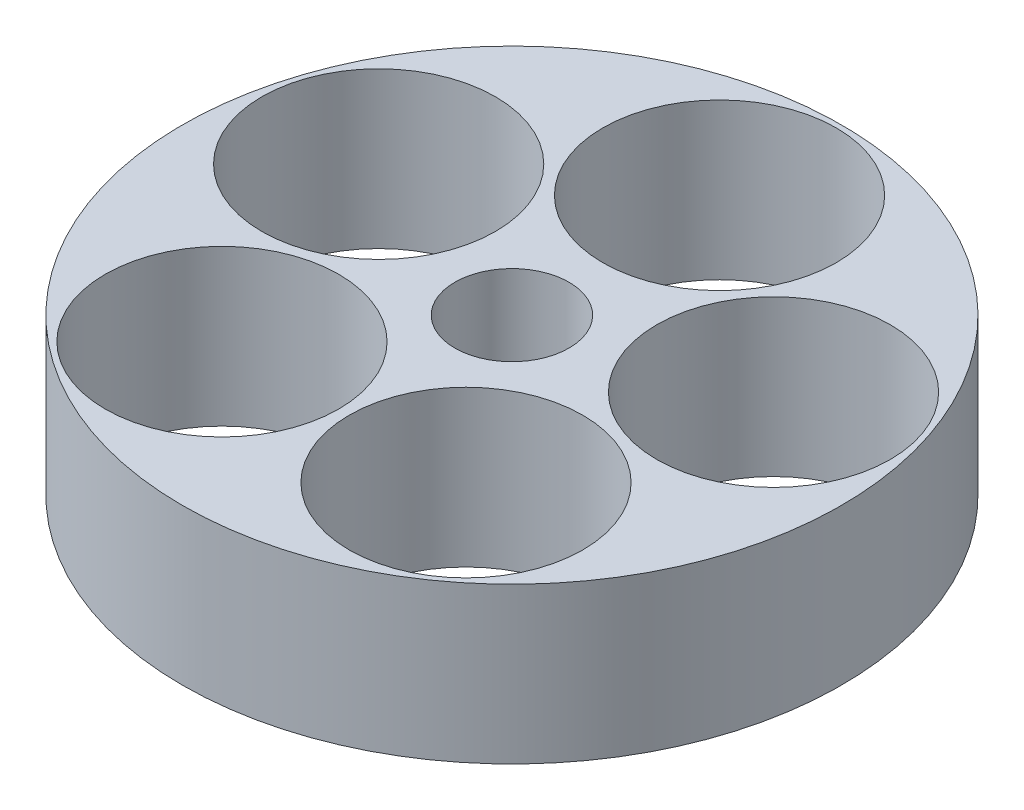
SolidWorks part; units mm, degrees
ref_plane "Front Plane" through (0, 0, 0) normal (0, 0, 1) x (1, 0, 0)
ref_plane "Top Plane" through (0, 0, 0) normal (0, 1, 0) x (1, 0, 0)
ref_plane "Right Plane" through (0, 0, 0) normal (1, 0, 0) x (0, 0, -1)
sketch "Sketch1" plane through (0, 0, 0) normal (0, 1, 0) x (1, 0, 0)
  line L0 (0, -164.5173) -> (0, 163.7587) construction
  line L1 (-104.9541, 34.1017) -> (106.3821, -34.5656) construction
  line L2 (-169.6132, -123.2312) -> (93.1873, 67.7046) construction
  line L3 (-107.5036, 0) -> (118.5963, 0) construction
  line L4 (-102.8693, -33.4243) -> (102.8693, 33.4243) construction
  line L5 (-62.7697, -86.3951) -> (62.7697, 86.3951) construction
  circle A0 centre (0, 0) radius 63.5
  circle A1 centre (38.0423, 12.3607) radius 22.5
  circle A4 centre (0, 40) radius 22.5
  circle A5 centre (-38.0423, 12.3607) radius 22.5
  circle A6 centre (-23.5114, -32.3607) radius 22.5
  circle A10 centre (23.5114, -32.3607) radius 22.5
  circle A11 centre (0, 0) radius 11
  dimension "D1" = 127
  dimension "D4" = 45
  dimension "D5" = 40
  dimension "D7" = 40
  dimension "D8" = 40
  dimension "D9" = 40
  dimension "D10" = 72
  dimension "D12" = 40
  dimension "D14" = 22
  dimension "D2" = 72
  dimension "D3" = 72
  dimension "D6" = 72
  dimension "D13" = 40
extrude "Boss-Extrude1" add sketch "Sketch1" along normal blind 30
sketch "Sketch2" plane through (0, 30, 0) normal (0, 1, 0) x (1, 0, 0)
  circle A0 centre (0, 0) radius 32.5
  circle A1 centre (0, 0) radius 50
  dimension "D1" = 65
  dimension "D2" = 100
sketch "Sketch3" plane through (0, 30, 0) normal (0, 1, 0) x (1, 0, 0)
  line L0 (-63.5, 0) -> (63.5, 0)
  line L1 (0, 63.5) -> (0, -63.5)
  circle A0 centre (0, 0) radius 63.5 construction
